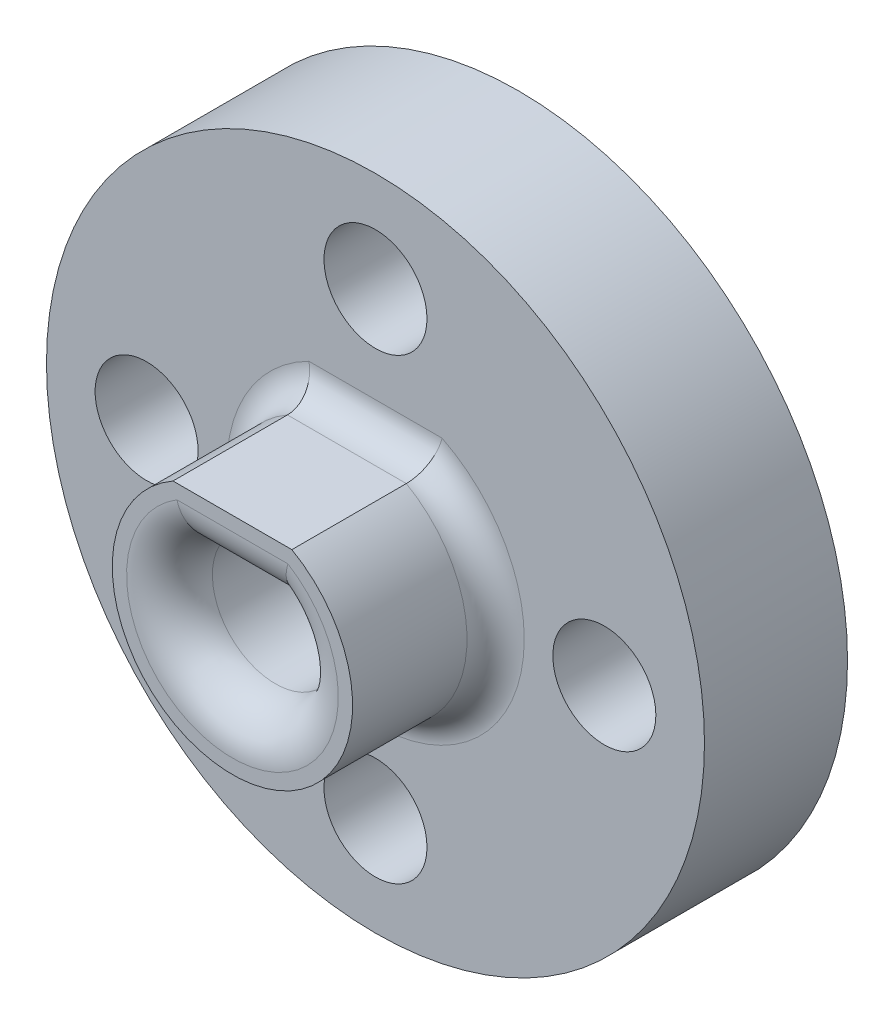
SolidWorks part; units mm, degrees
ref_plane "Front Plane" through (0, 0, 0) normal (0, 0, 1) x (1, 0, 0)
ref_plane "Top Plane" through (0, 0, 0) normal (0, 1, 0) x (1, 0, 0)
ref_plane "Right Plane" through (0, 0, 0) normal (1, 0, 0) x (0, 0, -1)
sketch "Sketch1" plane through (0, 0, 0) normal (0, 0, 1) x (1, 0, 0)
  line L0 (1.4552, 1.65) -> (-1.4552, 1.65)
  circle A0 centre (0, 8) radius 1.8
  circle A1 centre (8, 0) radius 1.8
  circle A2 centre (0, -8) radius 1.8
  circle A3 centre (-8, 0) radius 1.8
  circle A4 centre (0, 0) radius 11.5
  arc A5 (1.4552, 1.65) -> (-1.4552, 1.65) centre (0, 0) cw
  point P0 (0, 0)
  point P13 (0, 0)
  point P17 (0, -2.2)
  dimension "D1" = 3.6
  dimension "D4" = 23
  dimension "D5" = 2.2
  dimension "D2" = 8
  dimension "D6" = 3.85
  dimension "D3" = 4
extrude "Boss-Extrude1" add sketch "Sketch1" along normal blind 5 contours A4 A0 A1 A2 A3 L0 A5 region at (-11.1747, 0, 0)
extrude "Extrude-Thin1" add sketch "Sketch1<4>" along normal blind 5 from surface thin contours L0 A5 starting at face at (1.8, 8, 5) thin type one direction wall 2
sketch "Sketch1<4>" plane through (0, 0, 0) normal (0, 0, 1) x (1, 0, 0) same geometry as "Sketch1"
fillet "Fillet1" radius 1 2 edges at (0, -4.2, 5) (0, 3.65, 5)
fillet "Fillet2" radius 1.5 2 edges at (0, 1.65, 10) (0, -2.2, 10)
